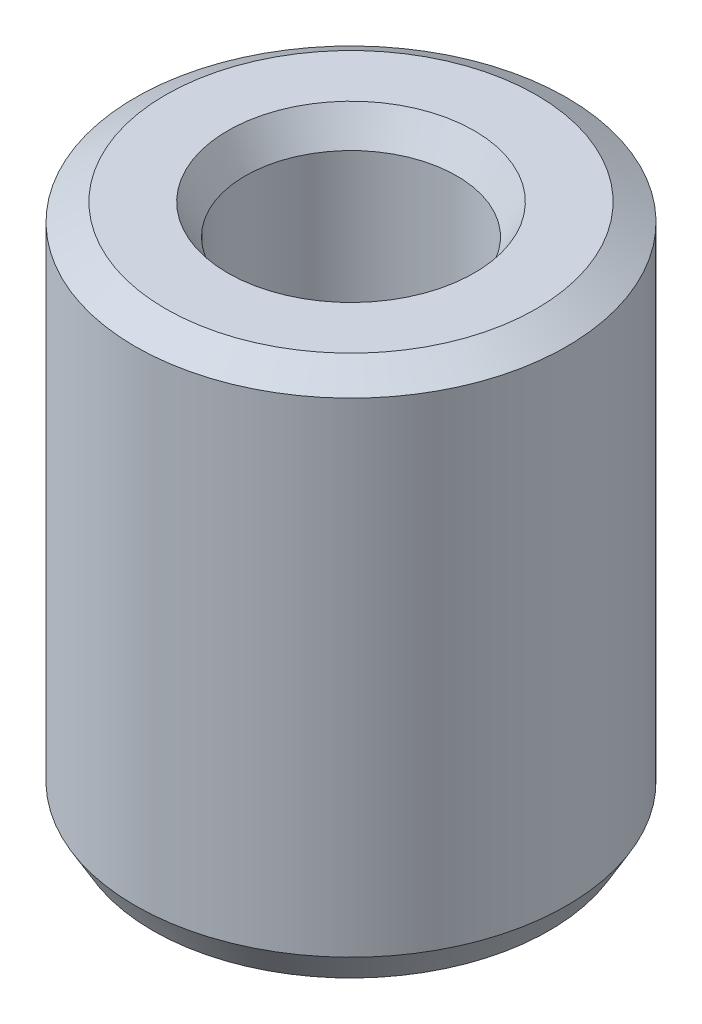
SolidWorks part; units mm, degrees
ref_plane "Front Plane" through (0, 0, 0) normal (0, 0, 1) x (1, 0, 0)
ref_plane "Top Plane" through (0, 0, 0) normal (0, 1, 0) x (1, 0, 0)
ref_plane "Right Plane" through (0, 0, 0) normal (1, 0, 0) x (0, 0, -1)
sketch "Sketch1" plane through (0, 0, 0) normal (0, 1, 0) x (1, 0, 0)
  circle A0 centre (0, 0) radius 30
  dimension "SLEEVE_OD" = 60
extrude "Boss-Extrude1" add sketch "Sketch1" along normal blind 74.0065
sketch "Sketch2" plane through (0, 0, 0) normal (0, 1, 0) x (1, 0, 0)
  circle A0 centre (0, 0) radius 14.7108
  dimension "BORE_D" = 29.4217
extrude "Cut-Extrude1" cut sketch "Sketch2" along normal through all
chamfer "Chamfer1" distance 2.4372 angle 60 4 edges at (0, 74.0065, 14.7108) (0, 0, 14.7108) (0, 0, 30) (0, 74.0065, 30) first distance on face at (0, 74.0065, 14.7108) first distance on face at (0, 0, 14.7108) first distance on face at (0, 74.0065, 30)
